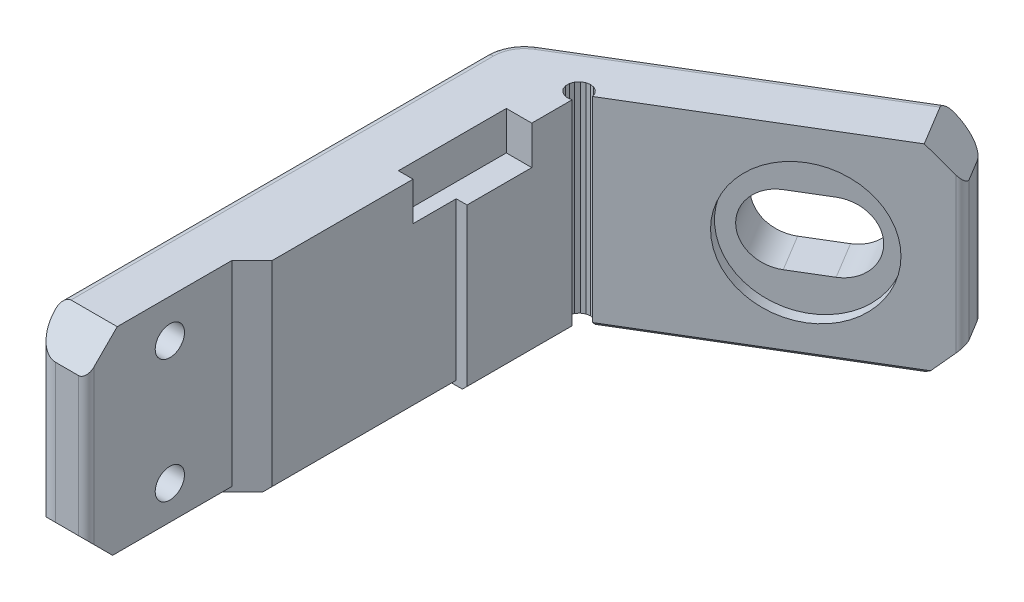
SolidWorks part; units mm, degrees
ref_plane "Front Plane" through (0, 0, 0) normal (0, 0, 1) x (1, 0, 0)
ref_plane "Top Plane" through (0, 0, 0) normal (0, 1, 0) x (1, 0, 0)
ref_plane "Right Plane" through (0, 0, 0) normal (1, 0, 0) x (0, 0, -1)
ref_plane "PY -20.700" through (0, -20.7, 0) normal (0, 1, 0) x (1, 0, 0)
sketch "leg and pad sketch" plane through (0, -20.7, 0) normal (0, 1, 0) x (1, 0, 0)
  line L0 (0.5513, 30.3327) -> (0.3673, 30.8194)
  line L1 (0.3673, 30.8194) -> (0.028, 31.2139)
  line L2 (0.028, 31.2139) -> (-0.4256, 31.4688)
  line L3 (-0.4256, 31.4688) -> (-0.939, 31.5534)
  line L4 (-0.939, 31.5534) -> (-1.4504, 31.4576)
  line L5 (-1.4504, 31.4576) -> (-1.8983, 31.1928)
  line L6 (-1.8983, 31.1928) -> (-2.2288, 30.7909)
  line L7 (-2.2288, 30.7909) -> (-2.4021, 30.3003)
  line L8 (-2.4021, 30.3003) -> (-2.3973, 29.78)
  line L9 (-2.3973, 29.78) -> (-2.2152, 29.2926)
  line L10 (-2.2152, 29.2926) -> (-1.8775, 28.8968)
  line L11 (-1.8775, 28.8968) -> (-1.4248, 28.6402)
  line L12 (-1.4248, 28.6402) -> (-0.9118, 28.5536)
  line L13 (-0.9118, 28.5536) -> (-0.4, 28.6475)
  line L14 (-0.4, 28.6475) -> (-0.4, -7.48)
  line L15 (-0.4, -7.48) -> (-4.42, -11.5)
  line L16 (-4.42, -11.5) -> (-4.42, -30.37)
  line L17 (-4.42, -30.37) -> (-11.42, -30.37)
  line L18 (-11.42, -30.37) -> (-11.42, 31.2838)
  line L19 (-11.42, 31.2838) -> (27.2048, 54.5947)
  line L20 (27.2048, 54.5947) -> (30.8218, 48.6015)
  line L21 (30.8218, 48.6015) -> (0.5513, 30.3327)
extrude "leg and pad" add sketch "leg and pad sketch" along normal mid plane 26
ref_plane "PX -1.350" through (-1.35, 0, 0) normal (1, 0, 0) x (0, 0, -1)
sketch "screw head relief sketch" plane through (-1.35, 0, 0) normal (1, 0, 0) x (0, 0, -1)
  line L0 (23.4, -12.7) -> (23.4, -6.7)
  line L1 (23.4, -6.7) -> (9.4, -6.7)
  line L2 (9.4, -6.7) -> (9.4, -12.7)
  line L3 (9.4, -12.7) -> (23.4, -12.7)
extrude "screw head relief" cut sketch "screw head relief sketch" against normal mid plane 4.7
sketch "lens frame relief, side sketch" plane through (0, -20.7, 0) normal (0, 1, 0) x (1, 0, 0)
  line L0 (1, 15) -> (-1.8, 15)
  line L1 (-1.8, 15) -> (-1.8, -8.88)
  line L2 (-1.8, -8.88) -> (1, -8.88)
  line L3 (1, -8.88) -> (1, 15)
extrude "lens frame relief, side" cut sketch "lens frame relief, side sketch" against normal mid plane 28
sketch "insert flange relief sketch" plane through (0, -20.7, 0) normal (0, 1, 0) x (1, 0, 0)
  line L0 (18.3249, 39.8914) -> (17.0331, 42.0318)
  line L1 (17.0331, 42.0318) -> (9.3276, 37.3814)
  line L2 (9.3276, 37.3814) -> (10.6194, 35.241)
  line L3 (10.6194, 35.241) -> (18.3249, 39.8914)
revolve "insert flange relief" cut sketch "insert flange relief sketch" angle 360 about L0
sketch "M6 slot end 1 sketch" plane through (0, -20.7, 0) normal (0, 1, 0) x (1, 0, 0)
  line L0 (20.4653, 41.1832) -> (15.8149, 48.8886)
  line L1 (15.8149, 48.8886) -> (11.9621, 46.5634)
  line L2 (11.9621, 46.5634) -> (16.6125, 38.858)
  line L3 (16.6125, 38.858) -> (20.4653, 41.1832)
revolve "M6 slot end 1" cut sketch "M6 slot end 1 sketch" angle 360 about L0
sketch "M6 slot end 2 sketch" plane through (0, -20.7, 0) normal (0, 1, 0) x (1, 0, 0)
  line L0 (16.1845, 38.5996) -> (11.5341, 46.3051)
  line L1 (11.5341, 46.3051) -> (7.6813, 43.9799)
  line L2 (7.6813, 43.9799) -> (12.3317, 36.2744)
  line L3 (12.3317, 36.2744) -> (16.1845, 38.5996)
revolve "M6 slot end 2" cut sketch "M6 slot end 2 sketch" angle 360 about L0
sketch "M6 slot middle sketch" plane through (0, -20.7, 0) normal (0, 1, 0) x (1, 0, 0)
  line L0 (16.1845, 38.5996) -> (20.4653, 41.1832)
  line L1 (20.4653, 41.1832) -> (15.8149, 48.8886)
  line L2 (15.8149, 48.8886) -> (11.5341, 46.3051)
  line L3 (11.5341, 46.3051) -> (16.1845, 38.5996)
extrude "M6 slot middle" cut sketch "M6 slot middle sketch" against normal mid plane 9
ref_plane "PX -7.920" through (-7.92, 0, 0) normal (1, 0, 0) x (0, 0, -1)
sketch "screw holes sketch" plane through (-7.92, 0, 0) normal (1, 0, 0) x (0, 0, -1)
  circle A0 centre (-19.54, -28.7) radius 1.9
  circle A1 centre (-19.54, -12.7) radius 1.9
extrude "screw holes" cut sketch "screw holes sketch" against normal mid plane 9
chamfer "leg top corners" distance 4 angle 45 2 edges at (-7.92, -7.7, 30.37) (-7.92, -33.7, 30.37) tangent propagation no
chamfer "pad end corners" distance 4 angle 45 2 edges at (29.0133, -7.7, -51.5981) (29.0133, -33.7, -51.5981) tangent propagation no
fillet "outside of the bend" radius 5 1 edges at (-11.42, -20.7, -31.2838) tangent propagation no
fillet "leg top outer edge" radius 3 1 edges at (-11.42, -20.7, 30.37) tangent propagation no
fillet "pad end outer edge" radius 3 1 edges at (27.2048, -20.7, -54.5947) tangent propagation no
fillet "leg top inner edge" radius 1 1 edges at (-4.42, -20.7, 30.37) tangent propagation no
fillet "pad end inner edge" radius 1 1 edges at (30.8218, -20.7, -48.6015) tangent propagation no
chamfer "bed face chamfer" distance 0.6 angle 45 7 edges at (13.9742, -33.7, -38.4337) (7.3883, -33.7, -42.635) (-4.42, -33.7, 18.935) (-1.8, -33.7, -3.06) (-0.4, -33.7, -21.8237) (-10.7742, -33.7, -30.9193) (-11.42, -33.7, -1.0457)
fillet "top face edge" radius 1 3 edges at (7.3883, -7.7, -42.635) (-10.7742, -7.7, -30.9193) (-11.42, -7.7, -1.0457)
equation "\"diffL\"= 608.8mm"
equation "\"diffW\"= 329.4mm"
equation "\"diffT\"= 2.9mm"
equation "\"chanSlotW\"= 12.9mm"
equation "\"chanSlotDepth\"= 11.13mm"
equation "\"chanFloor\"= 1.57mm"
equation "\"chanLeg\"= 12.7mm"
equation "\"lightL\"= 605mm"
equation "\"lightW\"= 331mm"
equation "\"lightH\"= 92mm"
equation "\"lightSideFlat\"= 30mm"
equation "\"lightSlopeLen\"= 33.1mm"
equation "\"lightWingDepth\"= 47.9mm"
equation "\"lightWingFlat\"= 90.2mm"
equation "\"lightChanW\"= 99.6mm"
equation "\"lightChanStand\"= 44.1mm"
equation "\"insFlangeD\"= 12.3mm"
equation "\"insFromEnd\"= 20.7mm"
equation "\"insUpSlope\"= 20.8mm"
equation "\"gaugeH\"= 10mm"
equation "\"gaugeStepLen\"= 14mm"
equation "\"gaugeStepW0\"= 13.1mm"
equation "\"gaugeStepDW\"= 0.2mm"
equation "\"gaugeSteps\"= 5mm"
equation "\"gaugeHandleLen\"= 30mm"
equation "\"gaugeHandleW\"= 24mm"
equation "\"gaugeSlot0\"= 3mm"
equation "\"gaugeSlotD\"= 0.1mm"
equation "\"gaugeSlotDepth\"= 8mm"
equation "\"gap\"= 25.4mm"
equation "\"edgeL\"= 1mm"
equation "\"edgeW\"= 0.75mm"
equation "\"proud\"= 1.5mm"
equation "\"seatClr\"= 0.15mm"
equation "\"tongueClrZ\"= 0.1mm"
equation "\"tongueClrX\"= 0.25mm"
equation "\"tongueLen\"= 30mm"
equation "\"armSide\"= 45mm"
equation "\"armEnd\"= 20mm"
equation "\"cornerCham\"= 3mm"
equation "\"brkW\"= 26mm"
equation "\"brkT\"= 7mm"
equation "\"brkSeatClr\"= 0.2mm"
equation "\"brkScrewSpan\"= 16mm"
equation "\"pilotD\"= 2.7mm"
equation "\"pilotDepth\"= 10mm"
equation "\"screwClrD\"= 3.9mm"
equation "\"jogBelow\"= 4mm"
equation "\"padT\"= 7mm"
equation "\"padLen\"= 31mm"
equation "\"m6Clr\"= 7mm"
equation "\"m6Slot\"= 3mm"
equation "\"flangeRelD\"= 17mm"
equation "\"flangeRelDepth\"= 1.5mm"
equation "\"relLen\"= 7mm"
equation "\"relDepth\"= 4mm"
equation "\"relLand\"= 2mm"
equation "\"knockN\"= 100mm"
equation "\"petgcfE\"= 3000mm"
equation "\"mockExtent\"= 110mm"
equation "\"relZnear\"= 9.4mm"
equation "\"relZfar\"= 23.4mm"
equation "\"headD\"= 8mm"
equation "\"headH\"= 2.5mm"
equation "\"headFromEnd\"= 6.8mm"
equation "\"headBack\"= 16.4mm"
equation "\"sideClr\"= 0.4mm"
equation "\"cornerRelR\"= 1.5mm"
equation "\"cornerRelBack\"= 0.6mm"
equation "\"endHeadH\"= 2.8mm"
equation "\"footClr\"= 1.2mm"
equation "\"footEndClr\"= 3.5mm"
equation "\"footLift\"= 6mm"
equation "\"footBlockClr\"= 0.5mm"
equation "\"footBack\"= 50mm"
equation "\"footFwd\"= 10mm"
equation "\"footBraceEnd\"= 3mm"
equation "\"footLoadN\"= 25mm"
equation "\"spacerLen\"= 60mm"
equation "\"spacerShort\"= 0.5mm"
equation "\"spacerCham\"= 0.8mm"
equation "\"spacerPerSide\"= 3mm"
equation "\"spacerPerEnd\"= 1mm"
equation "\"toolR\"= 9mm"
equation "\"visR\"= 4mm"
equation "\"edgeR\"= 1mm"
equation "\"bendOutR\"= 5mm"
equation "\"insideR\"= 2.5mm"
equation "\"footCornerR\"= 10mm"
equation "\"footFrontR\"= 8mm"
equation "\"braceKinkR\"= 12mm"
equation "\"bedCham\"= 1mm"
equation "\"bedChamSmall\"= 0.6mm"
equation "\"soleTopR\"= 2mm"
equation "\"cornerR\"= 6mm"
equation "\"rimInR\"= 1mm"
equation "\"insFlangeH\"= 1mm"
equation "\"insHoleFinishD\"= 4.5mm"
equation "\"insLen\"= 6.4mm"
equation "\"footToeTip\"= 4mm"
equation "\"cgInset\"= 4mm"
equation "\"lampWeightN\"= 51mm"
equation "\"frameWeightN\"= 10mm"
equation "\"bumpIn\"= 8mm"
equation "\"bumpH\"= 3mm"
equation "\"legBelowFront\"= 2mm"
equation "\"lipClr\"= 0.1mm"
equation "\"revealR\"= 2mm"
equation "\"frontCham\"= 1mm"
equation "\"leanDeg\" = 5mm"
equation "\"footTailT\" = 6mm"
equation "\"v1LeanDeg\" = 4.5mm"
equation "\"toeNoseR\" = 5mm"
equation "\"petgE\" = 2000mm"
equation "\"cheekT\" = 8mm"
equation "\"handleUp\" = 50mm"
equation "\"handleZ\" = -10mm"
equation "\"gripD\" = 19.05mm"
equation "\"gripClr\" = 0.5mm"
equation "\"bossWall\" = 5mm"
equation "\"bossLen\" = 14mm"
equation "\"socketFloor\" = 4mm"
equation "\"barEndClr\" = 1mm"
equation "\"lipH\" = 4mm"
equation "\"lipDeep\" = 6mm"
equation "\"stripT\" = 1.3mm"
equation "\"stripW\" = 12mm"
equation "\"stripClr\" = 0.5mm"
equation "\"stripBack\" = 3mm"
equation "\"endRelClr\" = 1mm"
equation "\"cornerScrewX\" = 5.5mm"
equation "\"cornerScrewZ\" = 6mm"
equation "\"cornerScrewD\" = 8.5mm"
equation "\"footTabIn\" = 33mm"
equation "\"footTabZ1\" = 50mm"
equation "\"footTabZ2\" = 19mm"
equation "\"footTabR\" = 8mm"
equation "\"landAx0\" = -17mm"
equation "\"landAz0\" = -30mm"
equation "\"landAx1\" = -3mm"
equation "\"landAz1\" = -18mm"
equation "\"landBx0\" = -60mm"
equation "\"landBz0\" = -43mm"
equation "\"landBx1\" = -46mm"
equation "\"landBz1\" = -27mm"
